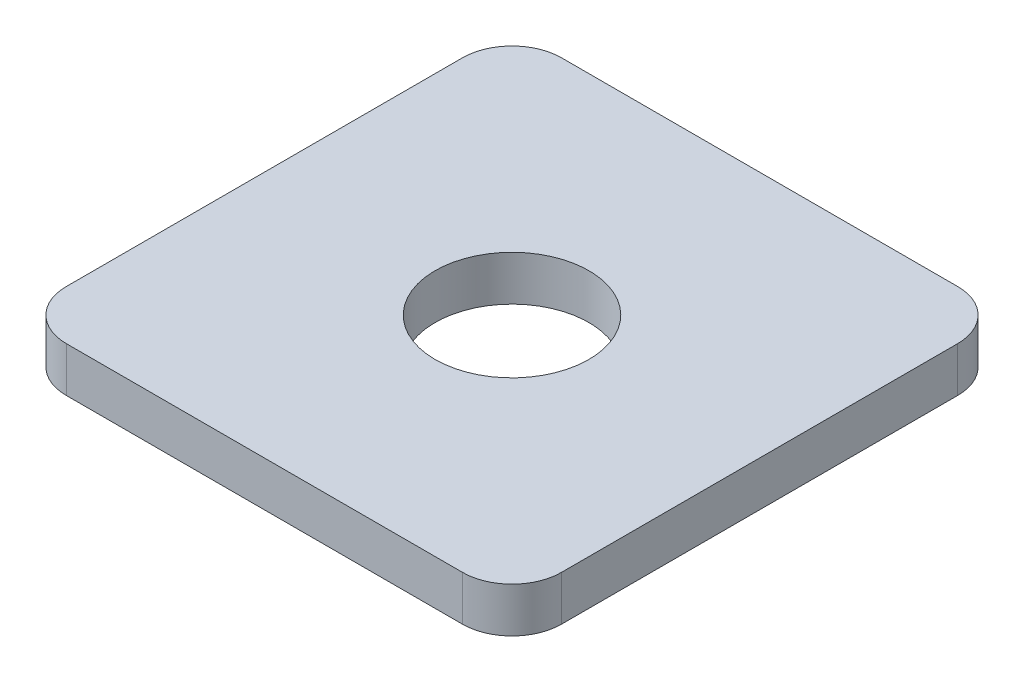
SolidWorks part; units mm, degrees
ref_plane "Front Plane" through (0, 0, 0) normal (0, 0, 1) x (1, 0, 0)
ref_plane "Top Plane" through (0, 0, 0) normal (0, 1, 0) x (1, 0, 0)
ref_plane "Right Plane" through (0, 0, 0) normal (1, 0, 0) x (0, 0, -1)
sketch "Sketch1" plane through (0, 0, 0) normal (0, 1, 0) x (1, 0, 0)
  line L1 (7, 0) -> (63, 0)
  line L2 (0, 7) -> (0, 63)
  line L3 (7, 70) -> (63, 70)
  line L4 (70, 7) -> (70, 63)
  arc A0 (63, 0) -> (70, 7) centre (63, 7) ccw
  arc A1 (7, 0) -> (0, 7) centre (7, 7) cw
  arc A2 (0, 63) -> (7, 70) centre (7, 63) cw
  arc A3 (63, 70) -> (70, 63) centre (63, 63) cw
  point P7 (70, 0)
  point P10 (0, 0)
  point P15 (70, 70)
  dimension "D3" = 7
  dimension "D1" = 70
  dimension "D2" = 70
extrude "Boss-Extrude1" add sketch "Sketch1" along normal blind 6.35
sketch "Sketch2" plane through (0, 6.35, 0) normal (0, 1, 0) x (1, 0, 0)
  line L0 (35, 70) -> (35, 0) construction
  line L1 (63, 70) -> (7, 70) construction
  line L2 (7, 0) -> (63, 0) construction
  line L3 (0, 35) -> (70, 35) construction
  line L4 (0, 63) -> (0, 7) construction
  line L5 (70, 7) -> (70, 63) construction
  circle A0 centre (35, 35) radius 10.875
  dimension "D1" = 21.75
extrude "Cut-Extrude1" cut sketch "Sketch2" against normal blind 6.35
